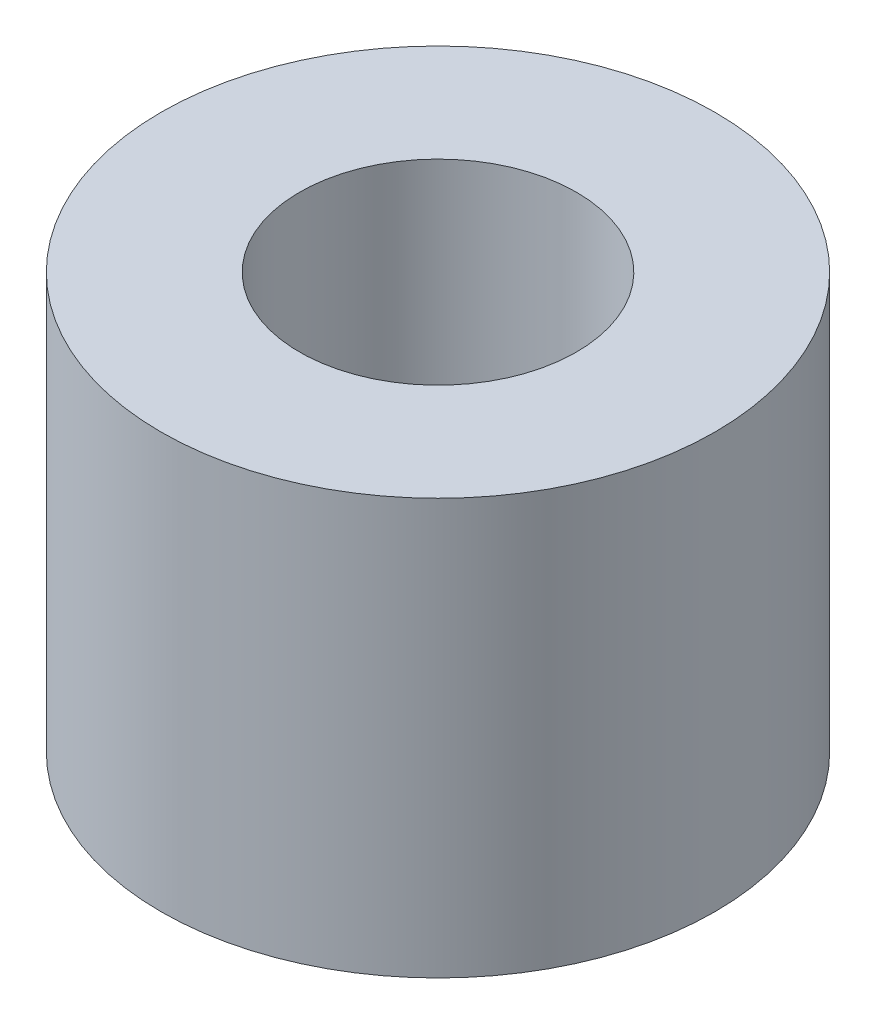
SolidWorks part; units mm, degrees
ref_plane "Front" through (0, 0, 0) normal (0, 0, 1) x (1, 0, 0)
ref_plane "Top" through (0, 0, 0) normal (0, 1, 0) x (1, 0, 0)
ref_plane "Right" through (0, 0, 0) normal (1, 0, 0) x (0, 0, -1)
ref_axis "side-side" through (80.9, 0, 0) along (-1, 0, 0)
ref_axis "up-down" through (0, 50, 0) along (0, -1, 0)
ref_axis "front-back" through (0, 0, -80.9) along (0, 0, 1)
sketch "Sketch1" plane through (0, 0, 0) normal (0, 1, 0) x (1, 0, 0)
  circle A0 centre (0, 0) radius 6.35
  circle A1 centre (0, 0) radius 3.175
  dimension "D1" = 6.35
  dimension "D2" = 12.7
extrude "Boss-Extrude1" add sketch "Sketch1" along normal mid plane 9.525
